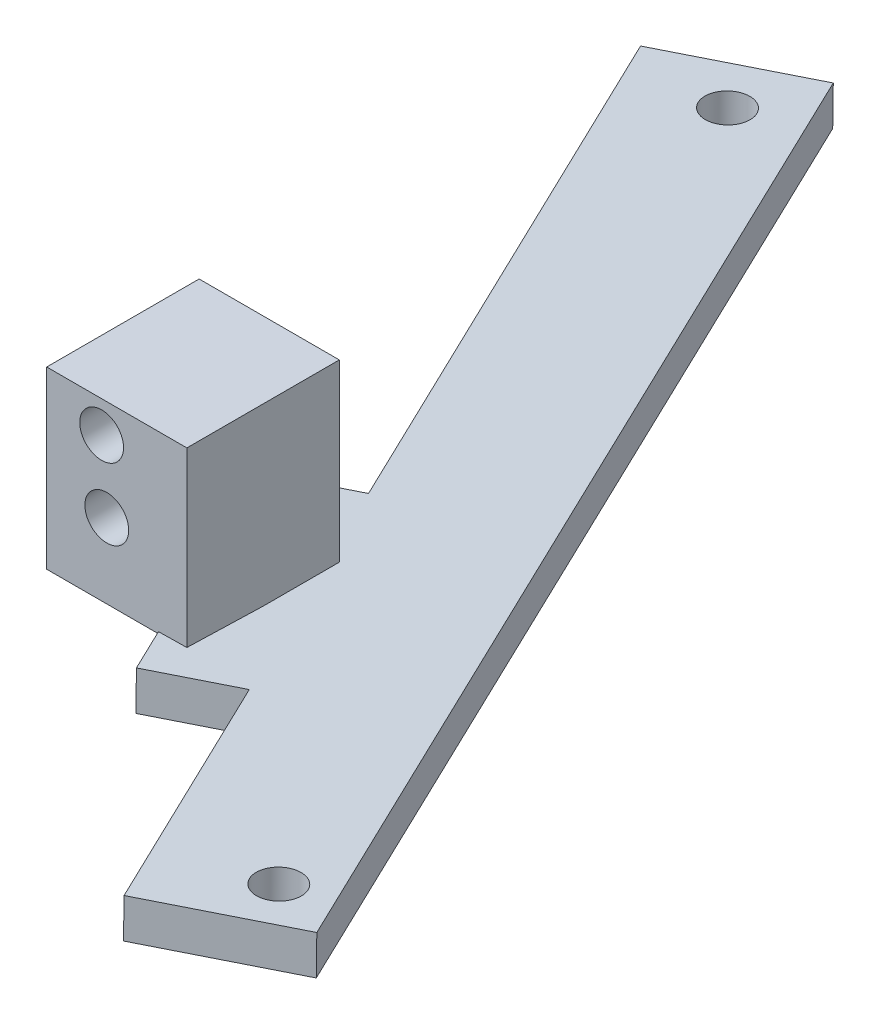
SolidWorks part; units mm, degrees
ref_plane "Front Plane" through (0, 0, 0) normal (0, 0, 1) x (1, 0, 0)
ref_plane "Top Plane" through (0, 0, 0) normal (0, 1, 0) x (1, 0, 0)
ref_plane "Right Plane" through (0, 0, 0) normal (1, 0, 0) x (0, 0, -1)
sketch "Sketch2" plane through (0, 0, 0) normal (0, 0, 1) x (1, 0, 0)
  line L0 (-194.337, 238.2488) -> (-194.337, 212.8488)
  line L1 (-194.337, 212.8488) -> (-174.017, 212.8488)
  line L2 (-174.017, 212.8488) -> (-174.017, 238.2488)
  line L3 (-174.017, 238.2488) -> (-194.337, 238.2488)
  circle A0 centre (-186.3724, 233.6772) radius 3.175
  circle A1 centre (-185.6285, 223.6772) radius 3.175
  dimension "D6" = 6.35
  dimension "D7" = 6.35
  dimension "D1" = 90
  dimension "D2" = 5.08
  dimension "D3" = 20.32
  dimension "D4" = 25.4
  dimension "D5" = 3.175
extrude "Boss-Extrude1" add sketch "Sketch2" along normal up to surface (22.098 mm away)
ref_plane "Plane1" through (-3.3927, 215.0063, -6.5391) normal (-0.0158, 0.9994, -0.0304) x (0.9999, 0.0158, -0.0005)
sketch "Sketch3" plane through (-3.3927, 215.0063, -6.5391) normal (-0.0158, 0.9994, -0.0304) x (0.9999, 0.0158, -0.0005)
  line L7 (-217.4516, 84.0765) -> (-198.8235, 93.3905)
  line L8 (-198.8235, 93.3905) -> (-123.8526, -56.5512)
  line L9 (-123.8526, -56.5512) -> (-142.4817, -65.8658)
  line L10 (-142.4817, -65.8658) -> (-160.6576, -29.5142)
  line L11 (-160.6576, -29.5142) -> (-171.5624, -34.9666)
  line L12 (-171.5624, -34.9666) -> (-188.869, -0.3535)
  line L13 (-188.869, -0.3535) -> (-177.9631, 5.0994)
  line L14 (-177.9631, 5.0994) -> (-217.4516, 84.0765)
  circle A0 centre (-132.9342, -52.9758) radius 3.175
  circle A1 centre (-203.0882, 82.3172) radius 3.175
  circle A2 centre (-132.9342, -52.9758) radius 3.175 construction
  circle A3 centre (-203.0882, 82.3172) radius 3.175 construction
  dimension "D6" = 5.3241
  dimension "D10" = 6.35
  dimension "D11" = 6.35
  dimension "D2" = 20.828
  dimension "D3" = 20.8268
  dimension "D4" = 33.02
  dimension "D5" = 45.115
  dimension "D7" = 167.64
  dimension "D8" = 38.6986
  dimension "D9" = 88.299
  dimension "D12" = 7.2594
extrude "Boss-Extrude2" add sketch "Sketch3" against normal blind 5.588
